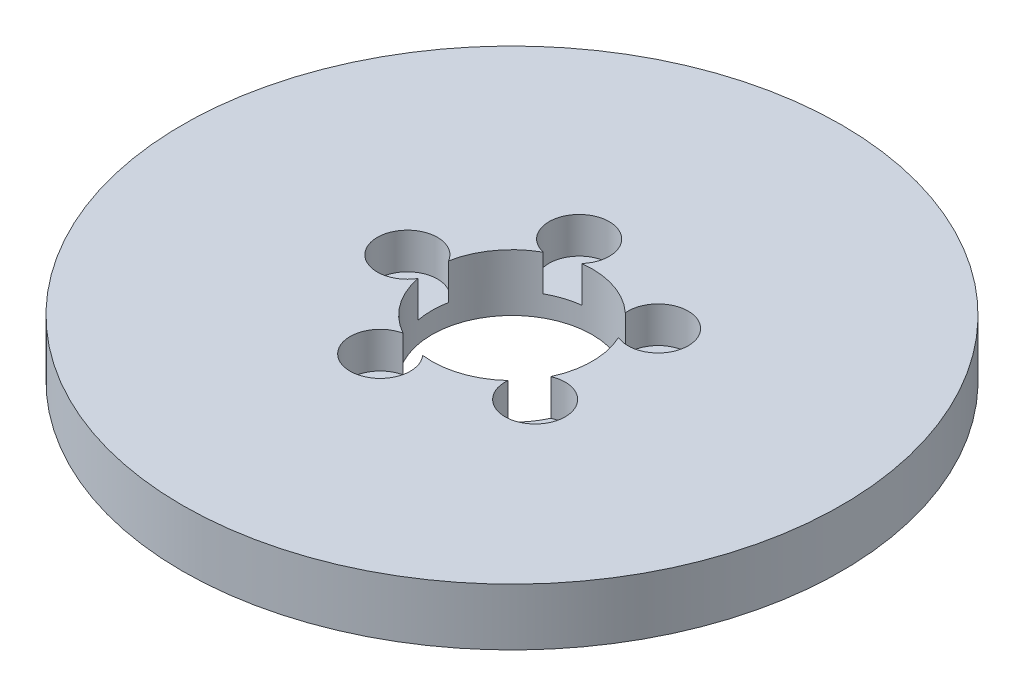
SolidWorks part; units mm, degrees
ref_plane "Front Plane" through (0, 0, 0) normal (0, 0, 1) x (1, 0, 0)
ref_plane "Top Plane" through (0, 0, 0) normal (0, 1, 0) x (1, 0, 0)
ref_plane "Right Plane" through (0, 0, 0) normal (1, 0, 0) x (0, 0, -1)
sketch "Sketch1" plane through (0, 0, 0) normal (0, 1, 0) x (1, 0, 0)
  circle A0 centre (0, 0) radius 92.5
  dimension "FLANGE_OD" = 185
extrude "Boss-Extrude1" add sketch "Sketch1" along normal blind 16
sketch "Sketch2" plane through (0, 0, 0) normal (0, 1, 0) x (1, 0, 0)
  circle A0 centre (0, 0) radius 22.5
  dimension "BORE_D" = 45
extrude "Cut-Extrude1" cut sketch "Sketch2" along normal through all
sketch "Sketch3" plane through (0, 16, 0) normal (0, 1, 0) x (1, 0, 0)
  circle A0 centre (0, 0) radius 29.3595 construction
  circle A1 centre (-29.3595, 0) radius 8.4477
  dimension "BOLT_D" = 16.8954
  dimension "BOLT_PCD" = 58.7189
extrude "Cut-Extrude2" cut sketch "Sketch3" against normal blind 10.1322
pattern_circular "CirPattern1" count 5 over 360 about axis through (0, 0, 0) along (0, 1, 0) of "Cut-Extrude2"
